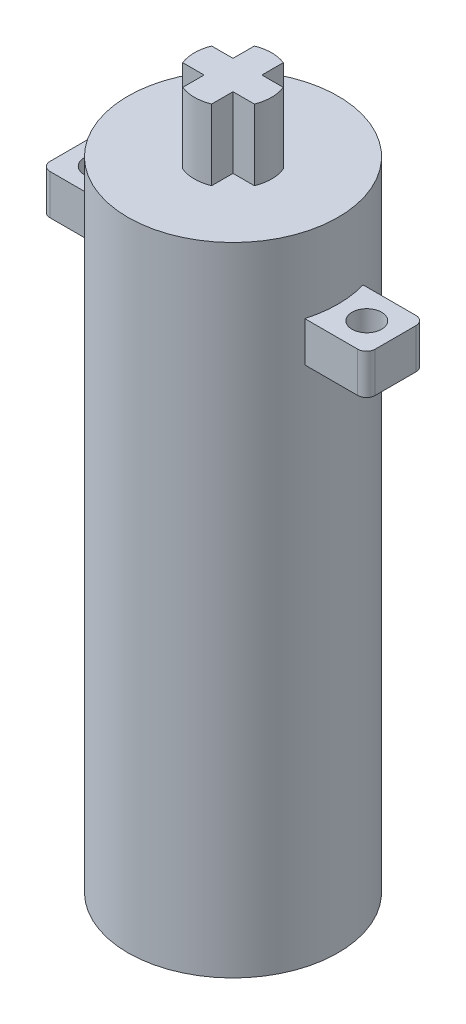
SolidWorks part; units mm, degrees
material "Plain Carbon Steel"
ref_plane "Front Plane" through (0, 0, 0) normal (0, 0, 1) x (1, 0, 0)
ref_plane "Top Plane" through (0, 0, 0) normal (0, 1, 0) x (1, 0, 0)
ref_plane "Right Plane" through (0, 0, 0) normal (1, 0, 0) x (0, 0, -1)
sketch "VigorSketch" plane through (0, 0, 0) normal (0, 1, 0) x (1, 0, 0)
  line L0 (0, -1.665) -> (0, 1.665)
  line L1 (-8.785, 1.665) -> (8.785, 1.665)
  line L2 (-9.285, 1.165) -> (-9.285, -1.165)
  line L3 (-8.785, -1.665) -> (8.785, -1.665)
  line L4 (9.285, 1.165) -> (9.285, -1.165)
  line L5 (2.0449, 0.8249) -> (0.8249, 0.8249)
  line L6 (0.8249, 0.8249) -> (0.8249, 2.0449)
  line L7 (-0.8249, 2.0449) -> (-0.8249, 0.8249)
  line L8 (-0.8249, 0.8249) -> (-2.0449, 0.8249)
  line L9 (-2.0449, -0.8249) -> (-0.8249, -0.8249)
  line L10 (-0.8249, -0.8249) -> (-0.8249, -2.0449)
  line L11 (2.0449, -0.8249) -> (0.8249, -0.8249)
  line L12 (0.8249, -0.8249) -> (0.8249, -2.0449)
  circle A0 centre (0, 0) radius 6
  arc A1 (-8.785, -1.665) -> (-9.285, -1.165) centre (-8.785, -1.165) cw
  arc A2 (9.285, -1.165) -> (8.785, -1.665) centre (8.785, -1.165) cw
  arc A3 (9.285, 1.165) -> (8.785, 1.665) centre (8.785, 1.165) ccw
  arc A4 (-8.785, 1.665) -> (-9.285, 1.165) centre (-8.785, 1.165) ccw
  circle A5 centre (7.6425, 0) radius 0.845
  circle A6 centre (-7.6425, 0) radius 0.845
  circle A7 centre (0, 0) radius 2.205
  point P7 (-9.285, 0)
  point P8 (9.285, 0)
  point P9 (0, 1.665)
  point P10 (0, -1.665)
  point P15 (9.285, -1.665)
  point P18 (9.285, 1.665)
  point P21 (-9.285, 1.665)
  point P40 (6, 0)
  dimension "D1" = 12
  dimension "D4" = 0.5
  dimension "D5" = 1.69
  dimension "D8" = 4.41
  dimension "D2" = 18.57
  dimension "D3" = 3.33
  dimension "D6" = 1.6425
  dimension "D7" = 1.665
  dimension "D9" = 1.22
extrude "VigorFlange" add sketch "VigorSketch" along normal blind 2.29 contours L1 A4 L2 A1 L3 A0 A6 | L1 A0 L3 L0 | L3 A0 L1 L0 | L4 A3 L1 A0 L3 A2 A5 region at (-3.9418, 0, 0) region at (3.9418, 0, 0) region at (-7.2747, 0, 1.6165) region at (5.9888, 0, 0.8476)
extrude "VigorAxle" add sketch "Sketch1<7>" along normal blind 10.62 contours L11 A7 L5 L6 L1 L0 L3 L12 | L8 A7 L9 L10 L3 L0 L1 L7 | L6 A7 L7 L1 | L10 A7 L12 L3 region at (-0.8902, 0, 0) region at (0, 0, 1.911) region at (0.8902, 0, 0) region at (0, 0, -1.911)
sketch "Sketch1<7>" plane through (0, 0, 0) normal (0, 1, 0) x (1, 0, 0) same geometry as "VigorSketch"
extrude "VigorBody" add sketch "VigorSketch<8>" along normal blind 6.58 and the other way blind 29.7899 contours A7 L1 A0 | A7 L3 A0 | L9 A7 L3 L10 | L1 A7 L8 L7 | L5 A7 L1 L6 | L3 A7 L11 L12 | L12 A7 L3 | L1 A7 L6 | L7 A7 L1 | L3 A7 L10 | A7 L1 A0 L3 | A7 L3 A0 L1 | L8 A7 L9 L10 L3 L0 L1 L7 | L11 A7 L5 L6 L1 L0 L3 L12 | L6 A7 L7 L1 | L10 A7 L12 L3 region at (-0.8902, 0, 0) region at (0, 0, 1.911) region at (0.8902, 0, 0) region at (0, 0, -1.911) region at (-1.044, 0, 1.7998) region at (-1.3254, 0, 1.2025) region at (1.3254, 0, 1.2025) region at (1.044, 0, 1.7998) region at (-1.3254, 0, -1.2025) region at (-1.044, 0, -1.7998) region at (1.044, 0, -1.7998) region at (1.3254, 0, -1.2025) region at (0, 0, 3.5146) region at (-3.9418, 0, 0) region at (3.9418, 0, 0) region at (0, 0, -3.5146)
sketch "VigorSketch<8>" plane through (0, 0, 0) normal (0, 1, 0) x (1, 0, 0) same geometry as "VigorSketch"
equation "\"vigorwidth\"= 0.472441in"
equation "\"D1@VigorSketch\"=\"vigorwidth\""
equation "\"vigorflangewidth\"= 0.731102in"
equation "\"D2@VigorSketch\"=\"vigorflangewidth\""
equation "\"vigorflangelength\"= 0.131102in"
equation "\"D3@VigorSketch\"=\"vigorflangelength\""
equation "\"vigorscrewsize\"= 0.066535in"
equation "\"D5@VigorSketch\"=\"vigorscrewsize\""
equation "\"vigorholeoffsetwid\"= 0.0646653in"
equation "\"D6@VigorSketch\"=\"vigorholeoffsetwid\""
equation "\"vigorholeoffsetlen\"= 0.065551in"
equation "\"D7@VigorSketch\"= \"vigorholeoffsetlen\""
equation "\"vigorflangedepth\"= 0.0901575in"
equation "\"vigordiscdepth\"= 0.0492126in"
equation "\"vigormotordepth\"= 1.12362in"
equation "\"vigortipdepth\"= 0.259055in"
equation "\"vigoraxlewidth\"= 0.173622in"
equation "\"D8@VigorSketch\"=\"vigoraxlewidth\""
equation "\"vigorcutlen\"= 0.0480315in"
equation "\"D9@VigorSketch\"=\"vigorcutlen\""
equation "\"vigoraxledepth\"= 0.159055in"
equation "\"D1@VigorBody\"=\"vigortipdepth\""
equation "\"D2@VigorBody\"=\"vigordiscdepth\"+\"vigormotordepth\""
equation "\"D1@VigorFlange\"=\"vigorflangedepth\""
equation "\"D1@VigorAxle\"=\"vigortipdepth\"+\"vigoraxledepth\""
equation "\"CageLeftBottomEdge\"=21.15mm"
equation "\"CageLeftTopEdge\"=22.11mm"
equation "\"CageRightBottomEdge\"=21.20mm"
equation "\"CageRightTopEdge\"=21.63mm"
equation "\"CageHeight\"=86.04mm"
equation "\"CageLength\"=73.76mm"
equation "\"CageTopScrewClearance\"=10mm"
equation "\"CageBottomScrewClearance\"=25mm"
equation "\"CageLeftTopDepth\"= 11.65mm"
equation "\"CageLeftBottomDepth\"=10.15mm"
equation "\"CageLeftTopHeight\"=10.56175mm"
equation "\"CageLeftBottomHeight\"=16mm"
equation "\"CageRightTopDepth\"= 11.15mm"
equation "\"CageRightBottomDepth\"=10.15mm"
equation "\"CageRightTopHeight\"=9.775mm"
equation "\"CageRightBottomHeight\"=15.49mm"
equation "\"CageLeftTopChannelDepth\"=2.41908mm"
equation "\"CageLeftBottomChannelDepth\"=2.588mm"
equation "\"CageLeftChannelHeight\"=11.7mm"
equation "\"CageRightTopChannelDepth\"=2.59mm"
equation "\"CageRightBottomChannelDepth\"=2.318mm"
equation "\"CageRightChannelHeight\"=10mm"
equation "\"CageChanRelHeight\"=23.99mm"
equation "\"CageChanRelDepth\"=5.492mm"
equation "\"CageChamberRadius\"=16.261mm"
equation "\"CageScrewDiameter\"=4.8mm"
equation "\"CageSetScrewDiameter\"=3.5mm"
equation "\"CageAxleRadius\"=6.639mm"
equation "\"CageAxleKeyHeight\"=1.619mm"
equation "\"CageAxleKeyWidth\"=2.662mm"
equation "\"CageHoseWindowWidth\"=16.29mm"
equation "\"CageHoseWindowHeight\"=26.5mm"
equation "\"CageHoseWindow-Edge\"=8.89mm"
equation "\"CageScrew-VerticalEdge\"=5.0mm"
equation "\"CageScrew-HorizontalEdge\"=7.5mm"
equation "\"CageScrew-HoseCornerScrewEdge\"=4.45mm"
equation "\"CageAxle-BottomEdge\"=56.05mm"
equation "\"CageAxle-FrontEdge\"=46.03mm"
equation "\"CageBackSetScrew-Axle\"=40mm"
equation "\"CageFrontSetScrew-Axle\"=22mm"
equation "\"CageVelocityWindow-BackEdge\"=34.8mm"
equation "\"CageVelocityWindow-BottomEdge\"=27.55mm"
equation "\"CageVelocityWindowHeight\"=22.29mm"
equation "\"CageVelocityWindowWidth\"=12.61mm"
equation "\"TriggerSlot-BottomEdge\"=6.35mm"
equation "\"TriggerSlot-FrontEdge\"=15mm"
equation "\"TriggerSlotSize\"=6.7mm"
